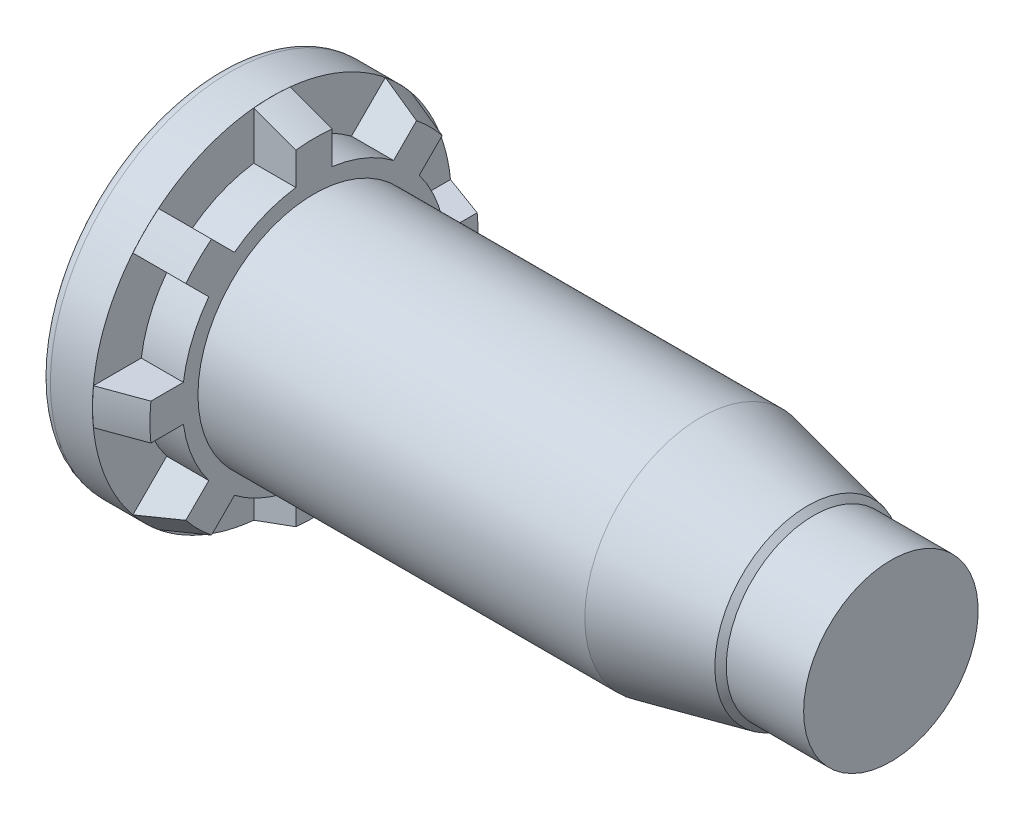
SolidWorks part; units mm, degrees
revolve "BaseBody" add sketch "BodySke" angle 360 about L6 other way angle 7.5
sketch "BodySke" plane through (0, 0, 0) normal (0, 0, 1) x (1, 0, 0)
  line L0 (-2.159, 6.9342) -> (-2.159, 0)
  line L1 (1.7272, 6.7357) -> (1.7272, 4.7625)
  line L2 (0.0025, 7.3635) -> (1.7272, 6.7357)
  line L3 (1.7272, 4.7625) -> (17.6022, 4.7625)
  line L4 (17.6022, 4.7625) -> (21.99, 3.8163)
  line L5 (25.4, 0) -> (-2.159, 0)
  line L6 (0, 0) -> (50.554, 0) construction
  line L7 (22.225, 3.5814) -> (25.4, 3.5814)
  line L8 (22.225, 3.5814) -> (21.99, 3.8163)
  line L9 (-1.7272, 7.366) -> (0, 7.366)
  line L10 (0.0025, 7.3635) -> (0, 7.3635)
  line L11 (1.5875, 19.05) -> (1.5875, -3.175) construction
  line L12 (0, 7.3635) -> (0, 7.366)
  line L13 (25.4, 3.5814) -> (25.4, 0)
  arc A0 (-2.159, 6.9342) -> (-1.7272, 7.366) centre (-1.7272, 6.9342) cw
  dimension "Fillet_rad" = 0.4318
  dimension "T_dim" = 2.159
  dimension "H_dia" = 14.732
  dimension "D2" = 0.0025
  dimension "D3" = 0.0025
  dimension "Advance" = 1.5875
  dimension "D1" = 20
  dimension "Length" = 25.4
  dimension "D4" = 45
  dimension "Diameter" = 9.525
  dimension "Minor_dia" = 7.6327
cosmetic thread "ThreadCosmetic" [suppressed] parameters "Thread_length"=18.0531, "Thread_minor"=7.6327
ref_plane "Plane1" through (0, 0, 0) normal (0, 0, 1) x (1, 0, 0)
ref_plane "Plane2" through (0, 0, 0) normal (0, 1, 0) x (1, 0, 0)
ref_plane "Plane3" through (0, 0, 0) normal (1, 0, 0) x (0, 0, -1)
sketch "ThdSchSke" plane through (0, 0, 0) normal (0, 0, 1) x (1, 0, 0)
  line L0 (3.937, -3.8163) -> (3.2745, -4.7625)
  line L1 (3.937, -3.8163) -> (4.5995, -4.7625)
  line L2 (4.5995, -4.7625) -> (4.5995, -5.9531)
  line L3 (-3.175, 0) -> (5.1513, 0) construction
  line L4 (0, -7.366) -> (0, 7.366) construction
  line L5 (4.5995, -5.9531) -> (3.2745, -5.9531)
  line L6 (3.2745, -5.9531) -> (3.2745, -4.7625)
  line L7 (21.9888, 6.5809) -> (21.9888, 1.1961) construction
  dimension "Thread_minor" = 7.6327
  dimension "Diameter" = 9.525
  dimension "Start" = 3.937
revolve "ThreadSchematic" [suppressed] cut sketch "ThdSchSke" angle 360 about L3
pattern_linear "ThdSchPat" [suppressed]
sketch "RibCutSke" plane through (1.7272, 1.7944, -0.091) normal (1, 0, 0) x (0, 0, -1)
  line L0 (0.6541, 3.5675) -> (0.6541, 5.5338)
  line L1 (3.1736, 2.5238) -> (4.5641, 3.9142)
  line L2 (0.6541, 2.9095) -> (0.6541, 2.4006) construction
  line L3 (-0.091, -1.7944) -> (-0.091, 5.0239) construction
  line L4 (-0.091, -1.7944) -> (0.6541, 2.9095) construction
  line L5 (-0.091, -1.7944) -> (2.7084, 2.0585) construction
  line L6 (2.7084, 2.0585) -> (2.3536, 1.7038) construction
  arc A1 (3.1736, 2.5238) -> (0.6541, 3.5675) centre (-0.091, -1.7944) ccw
  arc A2 (4.5641, 3.9142) -> (0.6541, 5.5338) centre (-0.091, -1.7944) ccw
  circle A3 centre (-0.091, -1.7944) radius 6.7357 construction
  circle A4 centre (-0.091, -1.7944) radius 4.7625 construction
  dimension "Rib_root_half_angle" = 9
  dimension "Rib_root_gap_angle" = 27
  dimension "Angle" = 45
extrude "RibCut" cut sketch "RibCutSke" against normal blind 1.7272
pattern_circular "RibCutsPat" count 8 every 45 about axis through (0, 0, 0) along (1, 0, 0) of "RibCut"
equation "' \"Length@BodySke\" = 1"
equation "' \"H_dia@BodySke\" = 0.58"
equation "' \"Start@ThdSchSke\" = 0.155"
equation "' \"T_dim@BodySke\" = 0.085"
equation "' \"Dog_dia@BodySke\" = 0.282"
equation "' \"Dog_len@BodySke\" = 0.125"
equation "' \"Thread_trans@BodySke\" = 0.182"
equation "' \"Diameter@BodySke\" = 0.375"
equation "' \"Minor_dia@BodySke\" =  0.3005"
equation "' \"Minor_dia@BodySke\" = 0.3005"
equation "' \"Advance@BodySke\" = 0.0625"
equation "\"Fillet_rad@BodySke\" =  \"T_dim@BodySke\" * 0.2"
equation "\"Clinch_ht@BodySke\" = \"T_dim@BodySke\" * 0.8"
equation "\"Num_ribs@RibCutsPat\" = 8"
equation "\"Angle@RibCutSke\" =\"Angle@RibCutsPat\""
equation "\"Rib_root_half_angle@RibCutSke\" = \"Angle@RibCutSke\" / 5"
equation "\"Rib_root_gap_angle@RibCutSke\" = \"Angle@RibCutSke\" - (2 * \"Rib_root_half_angle@RibCutSke\" )"
equation "\"Rib_root_dia@RibCutSke\" = \"Diameter@BodySke\""
equation "\"Inner_dia@RibCutSke\" = \"Diameter@BodySke\" + ( \"H_dia@BodySke\" - \"Diameter@BodySke\" ) / 4"
equation "\"Outer_dia@RibCutSke\" = \"H_dia@BodySke\""
equation "\"Depth@RibCut\" = \"Clinch_ht@BodySke\""
equation "\"Thread_length@ThreadCosmetic\" = \"Length@BodySke\" - \"Start@ThdSchSke\"  - \"Dog_len@BodySke\"  - ( \"Minor_dia@BodySke\" - \"Dog_dia@BodySke\" ) / 2"
equation "\"Thread_minor@ThreadCosmetic\" = \"Minor_dia@BodySke\""
equation "\"Thread_minor@ThdSchSke\" = \"Minor_dia@BodySke\""
equation "\"Diameter@ThdSchSke\" = \"Diameter@BodySke\""
equation "\"Overcut@ThdSchSke\" = \"Diameter@BodySke\" * 1.25"
equation "\"Num_threads@ThdSchPat\" = int( \"Thread_length@ThreadCosmetic\" / \"Advance@BodySke\" + 0.999 )  + 1"
equation "\"Advance@ThdSchPat\" = \"Thread_length@ThreadCosmetic\" /  (\"Num_threads@ThdSchPat\" - 1) 'relax it"
equation "\"Num_threads@ThdSchPat\" = \"Num_threads@ThdSchPat\" - sgn( \"Num_threads@ThdSchPat\" - 1) '---chamfered tips only---"
